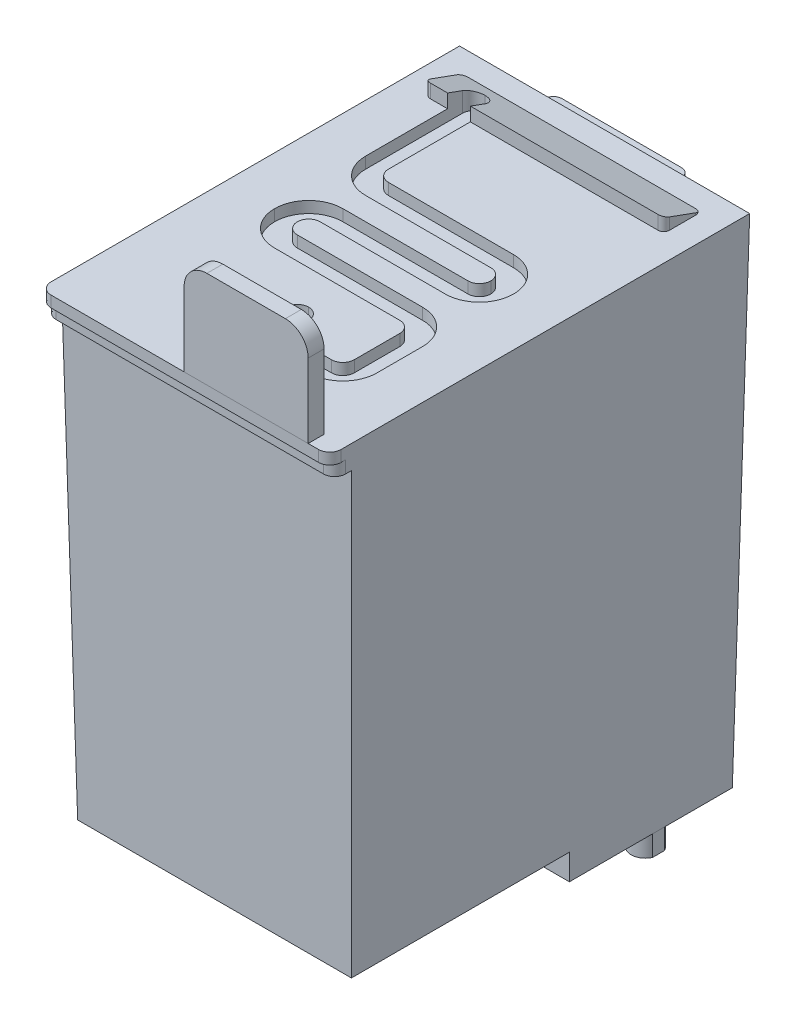
SolidWorks part; units mm, degrees
ref_plane "Front Plane" through (0, 0, 0) normal (0, 0, 1) x (1, 0, 0)
ref_plane "Top Plane" through (0, 0, 0) normal (0, 1, 0) x (1, 0, 0)
ref_plane "Right Plane" through (0, 0, 0) normal (1, 0, 0) x (0, 0, -1)
sketch "Sketch1" plane through (0, 0, 0) normal (0, 1, 0) x (1, 0, 0)
  line L0 (-12.75, 17.5) -> (12.75, -17.5) construction
  line L1 (-12.75, 17.5) -> (12.75, 17.5)
  line L2 (-12.75, 17.5) -> (-12.75, -17.5)
  line L3 (-12.75, -17.5) -> (12.75, -17.5)
  line L4 (12.75, 17.5) -> (12.75, -17.5)
  dimension "D1" = 25.5
  dimension "D2" = 35
extrude "Boss-Extrude1" add sketch "Sketch1" against normal blind 41.4 draft 1
sketch "Sketch2" plane through (0, -41.4, 0) normal (0, -1, 0) x (1, 0, 0)
  line L0 (-12.0274, -16.7774) -> (-12.0274, 16.7774) construction
  line L1 (12.0274, -16.7774) -> (-12.0274, -16.7774)
  line L2 (12.0274, -16.7774) -> (12.0274, -2.3774)
  line L3 (12.0274, -2.3774) -> (-12.0274, -2.3774)
  line L4 (-12.0274, -16.7774) -> (-12.0274, -2.3774)
  dimension "D1" = 14.4
extrude "Boss-Extrude2" add sketch "Sketch2" along normal blind 1.9 draft 1
sketch "Sketch3" plane through (0, -43.3, 0) normal (0, -1, 0) x (1, 0, 0)
  line L0 (-11.9942, -16.7442) -> (11.9942, -16.7442) construction
  line L1 (-5.2, -16.7442) -> (5.2, -16.7442)
  line L2 (-5.2, -16.7442) -> (-5.2, 16.7774)
  line L3 (-5.2, 16.7774) -> (5.2, 16.7774)
  line L4 (5.2, -16.7442) -> (5.2, 16.7774)
  line L5 (-12.0274, 16.7774) -> (12.0274, 16.7774) construction
  line L6 (0, 0) -> (0, 16.7774) construction
  dimension "D1" = 10.4
extrude "Boss-Extrude3" add sketch "Sketch3" along normal blind 1 and the other way up to next
sketch "Sketch4" plane through (5.2, 0, 0) normal (1, 0, 0) x (0, 0, -1)
  line L0 (16.7442, -43.3) -> (16.7267, -44.3)
  line L1 (16.7442, -44.3) -> (-16.7774, -44.3) construction
  line L2 (16.7267, -44.3) -> (16.7442, -44.3)
  line L3 (16.7442, -44.3) -> (16.7442, -43.3)
  line L4 (16.7442, -43.3) -> (17.5, 0) construction
extrude "Cut-Extrude1" cut sketch "Sketch4" against normal through all
sketch "Sketch5" plane through (0, -44.3, 0) normal (0, -1, 0) x (1, 0, 0)
  line L0 (5.2, -16.7267) -> (5.2, 16.7774) construction
  line L1 (-5.2, 16.7774) -> (5.2, 16.7774)
  line L2 (-5.2, 16.7774) -> (-5.2, -1.2267)
  line L3 (-5.2, -1.2267) -> (5.2, -1.2267)
  line L4 (5.2, 16.7774) -> (5.2, -1.2267)
  line L5 (-5.2, -16.7267) -> (5.2, -16.7267) construction
  dimension "D1" = 15.5
extrude "Boss-Extrude4" add sketch "Sketch5" along normal blind 0.4
sketch "Sketch6" plane through (5.2, 0, 0) normal (1, 0, 0) x (0, 0, -1)
  line L0 (-16.7774, -41.4) -> (-11.0616, -44.7)
  line L1 (1.2267, -44.7) -> (-16.7774, -44.7) construction
  line L2 (-11.0616, -44.7) -> (-16.7774, -44.7)
  line L3 (-16.7774, -44.7) -> (-16.7774, -41.4)
  dimension "D1" = 30
extrude "Cut-Extrude2" cut sketch "Sketch6" against normal through all
sketch "Sketch7" plane through (0, -44.7, 0) normal (0, -1, 0) x (1, 0, 0)
  line L0 (5.2, 16.7774) -> (-5.2, 16.7774) construction
  line L1 (-3.5, 16.7774) -> (3.5, 16.7774)
  line L2 (-3.5, 16.7774) -> (-3.5, 12.2774)
  line L3 (-3.5, 12.2774) -> (3.5, 12.2774)
  line L4 (3.5, 16.7774) -> (3.5, 12.2774)
  line L5 (0, 12.2774) -> (0, 11.0616) construction
  line L6 (-5.2, 11.0616) -> (5.2, 11.0616) construction
  dimension "D1" = 4.5
  dimension "D2" = 7
extrude "Cut-Extrude3" cut sketch "Sketch7" against normal up to surface (3.3 mm away) up to face at (-7.7603, -41.4, 4.8057)
sketch "Sketch8" plane through (0, -44.7, 0) normal (0, -1, 0) x (1, 0, 0)
  line L0 (0, 0) -> (0, -14.7267) construction
  line L1 (-4.2, 10.2774) -> (4.2, 10.2774)
  line L2 (-4.2, 10.2774) -> (-4.2, -14.7267)
  line L3 (-4.2, -14.7267) -> (4.2, -14.7267)
  line L4 (4.2, 10.2774) -> (4.2, -14.7267)
  line L5 (-5.2, -16.7267) -> (5.2, -16.7267) construction
  line L6 (-3.5, 12.2774) -> (3.5, 12.2774) construction
  dimension "D1" = 8.4
  dimension "D2" = 2
  dimension "D3" = 2
extrude "Cut-Extrude4" cut sketch "Sketch8" against normal blind 1.3
sketch "Sketch9" plane through (0, -43.3, 0) normal (0, -1, 0) x (1, 0, 0)
  line L0 (-11.9942, -16.7442) -> (-5.2, -16.7442) construction
  line L1 (-11.9942, -2.4105) -> (-9.6942, -2.4105)
  line L2 (-11.9942, -2.4105) -> (-11.9942, -16.7442)
  line L3 (-11.9942, -16.7442) -> (-9.6942, -16.7442)
  line L4 (-9.6942, -2.4105) -> (-9.6942, -16.7442)
  line L5 (5.2, -16.7442) -> (11.9942, -16.7442) construction
  line L6 (11.9942, -2.4105) -> (9.6942, -2.4105)
  line L7 (11.9942, -2.4105) -> (11.9942, -16.7442)
  line L8 (11.9942, -16.7442) -> (9.6942, -16.7442)
  line L9 (9.6942, -2.4105) -> (9.6942, -16.7442)
  dimension "D1" = 2.3
extrude "Boss-Extrude5" add sketch "Sketch9" along normal blind 0.4 draft 1
sketch "Sketch10" plane through (0, -43.7, 0) normal (0, -1, 0) x (1, 0, 0)
  line L0 (11.9872, -9.7183) -> (11.9872, -10.7561)
  line L1 (11.9872, -16.7372) -> (11.9872, -2.4175) construction
  line L2 (10.85, -10.2372) -> (-10.85, -10.2372) construction
  line L3 (0, -10.2372) -> (0, 0) construction
  line L4 (-11.9872, -16.7372) -> (-9.7012, -16.7372) construction
  circle A0 centre (-10.85, -10.2372) radius 1.25
  arc A1 (11.9872, -9.7183) -> (11.9872, -10.7561) centre (10.85, -10.2372) ccw
  dimension "D1" = 2.5
  dimension "D2" = 21.7
  dimension "D3" = 6.5
extrude "Boss-Extrude6" add sketch "Sketch10" along normal blind 1.8 and the other way up to next (43.7 mm away)
sketch "Sketch11" plane through (0, 0, 0) normal (0, 0, 1) x (1, 0, 0)
  line L0 (0, -1) -> (0, 0) construction
  line L1 (6, -1) -> (-6, -1)
  line L2 (6, -1) -> (6, -2.1)
  line L3 (6, -2.1) -> (-6, -2.1)
  line L4 (-6, -1) -> (-6, -2.1)
  line L5 (12.75, 0) -> (-12.75, 0) construction
  dimension "D1" = 12
  dimension "D2" = 1.1
  dimension "D3" = 1
extrude "Boss-Extrude7" add sketch "Sketch11" against normal blind 19
fillet "Fillet1" radius 0.75 2 edges at (-6, -1.55, -19) (6, -1.55, -19)
sketch "Sketch12" plane through (0, 0, 0) normal (0, 1, 0) x (1, 0, 0)
  line L0 (0, 12.2) -> (0, 0) construction
  line L1 (-10, 15.5) -> (10, 15.5)
  line L2 (-10.5, 15) -> (-10.5, 12.7)
  line L3 (-10, 12.2) -> (10, 12.2)
  line L4 (10.5, 15) -> (10.5, 12.7)
  line L5 (12.75, 17.5) -> (-12.75, 17.5) construction
  arc A0 (10, 15.5) -> (10.5, 15) centre (10, 15) cw
  arc A1 (-10.5, 12.7) -> (-10, 12.2) centre (-10, 12.7) ccw
  arc A2 (10, 12.2) -> (10.5, 12.7) centre (10, 12.7) ccw
  arc A3 (-10, 15.5) -> (-10.5, 15) centre (-10, 15) ccw
  dimension "D1" = 0.5
  dimension "D2" = 3.3
  dimension "D3" = 21
  dimension "D4" = 2
extrude "Boss-Extrude8" add sketch "Sketch12" along normal blind 1.5
chamfer "Chamfer1" distance 1.5 angle 70 1 edges at (0, 1.5, -15.5) tangent propagation no first distance on face at (0, 0.75, -15.5)
sketch "Sketch13" plane through (0, 0, 0) normal (0, 1, 0) x (1, 0, 0)
  line L0 (-12.75, 17.5) -> (-12.75, -17.5) construction
  line L1 (-12.75, 0) -> (12.75, 0)
  line L2 (-12.75, 0) -> (-12.75, -18.4)
  line L3 (-11.75, -19.4) -> (11.75, -19.4)
  line L4 (12.75, 0) -> (12.75, -18.4)
  line L5 (12.75, -17.5) -> (12.75, 17.5) construction
  line L6 (-12.75, -17.5) -> (12.75, -17.5) construction
  arc A0 (-12.75, -18.4) -> (-11.75, -19.4) centre (-11.75, -18.4) ccw
  arc A1 (11.75, -19.4) -> (12.75, -18.4) centre (11.75, -18.4) ccw
  dimension "D1" = 1
  dimension "D2" = 1.9
extrude "Boss-Extrude9" add sketch "Sketch13" against normal blind 1 draft 1
sketch "Sketch14" plane through (0, 0, 0) normal (0, 1, 0) x (1, 0, 0)
  line L0 (-12.75, 17.5) -> (-12.75, -18.4) construction
  line L1 (-12.75, -0.45) -> (12.75, -0.45)
  line L2 (-12.75, -0.45) -> (-12.75, -17.9825)
  line L3 (-11.75, -18.9825) -> (11.75, -18.9825)
  line L4 (12.75, -0.45) -> (12.75, -17.9825)
  line L5 (12.75, -18.4) -> (12.75, 17.5) construction
  line L6 (12.7325, -17.4825) -> (-12.7325, -17.4825) construction
  arc A0 (-12.75, -17.9825) -> (-11.75, -18.9825) centre (-11.75, -17.9825) ccw
  arc A1 (11.75, -18.9825) -> (12.75, -17.9825) centre (11.75, -17.9825) ccw
  point P12 (12.75, -18.9825)
  dimension "D1" = 1
  dimension "D2" = 1.5
extrude "Boss-Extrude10" add sketch "Sketch14" against normal blind 2.1 draft 1
sketch "Sketch15" plane through (0, 0, 0) normal (0, 1, 0) x (1, 0, 0)
  line L0 (-11.75, -19.4) -> (11.75, -19.4) construction
  line L1 (10.85, -19.4) -> (-0.05, -19.4)
  line L2 (10.85, -19.4) -> (10.85, -18)
  line L3 (10.85, -18) -> (-0.05, -18)
  line L4 (-0.05, -19.4) -> (-0.05, -18)
  line L6 (-12.75, 17.5) -> (-12.75, -18.4) construction
  dimension "D1" = 10.9
  dimension "D2" = 23.6
  dimension "D3" = 1.4
extrude "Boss-Extrude11" add sketch "Sketch15" along normal blind 8.5
fillet "Fillet2" radius 2 2 edges at (10.85, 8.5, 18.7) (-0.05, 8.5, 18.7)
sketch "Sketch16" plane through (0, 0, 0) normal (0, 1, 0) x (1, 0, 0)
  line L0 (-8.5, 14.5) -> (-8.5, 2)
  line L1 (-8.5, 2) -> (6.5, 2)
  line L2 (6.5, 2) -> (6.5, 0)
  line L3 (6.5, 0) -> (-8.5, 0)
  line L4 (-8.5, 0) -> (-8.5, -6)
  line L5 (-8.5, -6) -> (6.5, -6)
  line L6 (6.5, -6) -> (6.5, -12)
  line L7 (6.5, -12) -> (1.5, -12)
  line L8 (1.5, -12) -> (1.5, -9)
  line L9 (1.5, -9) -> (-0.5, -9)
  line L10 (-0.5, -9) -> (-0.5, -14)
  line L11 (-0.5, -14) -> (8.5, -14)
  line L12 (8.5, -14) -> (8.5, -4)
  line L13 (8.5, -4) -> (-6.5, -4)
  line L14 (-6.5, -4) -> (-6.5, -2)
  line L15 (-6.5, -2) -> (8.5, -2)
  line L16 (8.5, -2) -> (8.5, 4)
  line L17 (8.5, 4) -> (-6.5, 4)
  line L18 (-6.5, 4) -> (-6.5, 14.5)
  line L19 (-6.5, 14.5) -> (-8.5, 14.5)
  line L20 (-6.5, 4) -> (-6.5, 2) construction
  line L21 (6.5, 2) -> (8.5, 2) construction
  line L22 (6.5, 0) -> (6.5, -2) construction
  line L23 (-6.5, -2) -> (-8.5, -2) construction
  line L24 (6.5, -6) -> (6.5, -4) construction
  line L25 (6.5, -12) -> (8.5, -12) construction
  line L26 (1.5, -12) -> (1.5, -14) construction
  line L27 (10, 15.5) -> (-10, 15.5) construction
  line L28 (-10.5, 15) -> (-10.5, 12.7) construction
  line L29 (1, -2) -> (-1, 0) construction
  line L30 (0, -1) -> (0, 0) construction
  dimension "D1" = 2
  dimension "D2" = 1
  dimension "D3" = 2
  dimension "D4" = 2
  dimension "D5" = 2
  dimension "D6" = 5
  dimension "D7" = 3
  dimension "D8" = 10.5
  dimension "D9" = 3
extrude "Cut-Extrude5" cut sketch "Sketch16" against normal blind 1 and the other way through all
fillet "Fillet3" radius 1 12 edges at (-0.5, -0.5, 9) (1.5, -0.5, 9) (1.5, -0.5, 12) (6.5, -0.5, 12) (6.5, -0.5, 6) (-6.5, -0.5, 2) (-6.5, -0.5, 4) (6.5, -0.5, 0) (6.5, -0.5, -2) (-6.5, -0.5, -4) (-8.5, -0.318, -14.5) (-6.5, -0.318, -14.5)
fillet "Fillet4" radius 3 8 edges at (-8.5, -0.5, -2) (8.5, -0.5, 14) (-0.5, -0.5, 14) (8.5, -0.5, 4) (8.5, -0.5, -4) (8.5, -0.5, 2) (-8.5, -0.5, 6) (-8.5, -0.5, 0)
sketch "Sketch17" plane through (0, -43.4, 0) normal (0, -1, 0) x (1, 0, 0)
  line L1 (-3.25, 10.0774) -> (3.25, 10.0774)
  line L2 (-3.25, 10.0774) -> (-3.25, -14.5267)
  line L3 (-3.25, -14.5267) -> (3.25, -14.5267)
  line L4 (3.25, 10.0774) -> (3.25, -14.5267)
  line L5 (0, -14.5267) -> (0, -14.7267) construction
  line L6 (-4.2, -14.7267) -> (4.2, -14.7267) construction
  line L7 (0, 10.0774) -> (0, 10.2774) construction
  line L8 (4.2, 10.2774) -> (-4.2, 10.2774) construction
  dimension "D1" = 0.2
  dimension "D2" = 6.5
extrude "Boss-Extrude12" add sketch "Sketch17" along normal blind 1
sketch "Sketch18" plane through (0, -44.4, 0) normal (0, -1, 0) x (1, 0, 0)
  line L0 (3.25, 10.0774) -> (-3.25, 10.0774) construction
  line L1 (-1.35, 9.8774) -> (3.05, 9.8774)
  line L2 (-1.35, 9.8774) -> (-1.35, 2.3774)
  line L3 (-1.35, 2.3774) -> (3.05, 2.3774)
  line L4 (3.05, 9.8774) -> (3.05, 2.3774)
  line L5 (3.25, -14.5267) -> (3.25, 10.0774) construction
  dimension "D1" = 4.4
  dimension "D2" = 7.5
  dimension "D3" = 0.2
  dimension "D4" = 0.2
extrude "Boss-Extrude13" add sketch "Sketch18" along normal blind 0.1
sketch "Sketch19" plane through (0, -44.4, 0) normal (0, -1, 0) x (1, 0, 0)
  line L0 (-2.15, -13.9017) -> (1.8, -13.9017) construction
  line L1 (-3.15, -13.4767) -> (-2.15, -13.4767)
  line L2 (-3.15, -13.4767) -> (-3.15, -14.3267)
  line L3 (-3.15, -14.3267) -> (-2.15, -14.3267)
  line L4 (-2.15, -13.4767) -> (-2.15, -14.3267)
  line L5 (1.8, -13.4767) -> (2.8, -13.4767)
  line L6 (1.8, -13.4767) -> (1.8, -14.3267)
  line L7 (1.8, -14.3267) -> (2.8, -14.3267)
  line L8 (2.8, -13.4767) -> (2.8, -14.3267)
  line L9 (-3.25, 10.0774) -> (-3.25, -14.5267) construction
  line L10 (3.25, -14.5267) -> (3.25, 10.0774) construction
  line L11 (-3.25, -14.5267) -> (3.25, -14.5267) construction
  line L12 (-3.15, -12.0851) -> (-2.15, -12.0851)
  line L13 (-3.15, -12.0851) -> (-3.15, -12.9351)
  line L14 (-3.15, -12.9351) -> (-2.15, -12.9351)
  line L15 (-2.15, -12.0851) -> (-2.15, -12.9351)
  line L16 (-3.15, -10.6934) -> (-2.15, -10.6934)
  line L17 (-3.15, -10.6934) -> (-3.15, -11.5434)
  line L18 (-3.15, -11.5434) -> (-2.15, -11.5434)
  line L19 (-2.15, -10.6934) -> (-2.15, -11.5434)
  line L20 (-3.15, -9.3017) -> (-2.15, -9.3017)
  line L21 (-3.15, -9.3017) -> (-3.15, -10.1517)
  line L22 (-3.15, -10.1517) -> (-2.15, -10.1517)
  line L23 (-2.15, -9.3017) -> (-2.15, -10.1517)
  line L24 (-3.15, -7.9101) -> (-2.15, -7.9101)
  line L25 (-3.15, -7.9101) -> (-3.15, -8.7601)
  line L26 (-3.15, -8.7601) -> (-2.15, -8.7601)
  line L27 (-2.15, -7.9101) -> (-2.15, -8.7601)
  line L28 (-3.15, -6.5184) -> (-2.15, -6.5184)
  line L29 (-3.15, -6.5184) -> (-3.15, -7.3684)
  line L30 (-3.15, -7.3684) -> (-2.15, -7.3684)
  line L31 (-2.15, -6.5184) -> (-2.15, -7.3684)
  line L32 (-3.15, -5.1267) -> (-2.15, -5.1267)
  line L33 (-3.15, -5.1267) -> (-3.15, -5.9767)
  line L34 (-3.15, -5.9767) -> (-2.15, -5.9767)
  line L35 (-2.15, -5.1267) -> (-2.15, -5.9767)
  line L36 (1.8, -12.0851) -> (2.8, -12.0851)
  line L37 (1.8, -12.0851) -> (1.8, -12.9351)
  line L38 (1.8, -12.9351) -> (2.8, -12.9351)
  line L39 (2.8, -12.0851) -> (2.8, -12.9351)
  line L40 (1.8, -10.6934) -> (2.8, -10.6934)
  line L41 (1.8, -10.6934) -> (1.8, -11.5434)
  line L42 (1.8, -11.5434) -> (2.8, -11.5434)
  line L43 (2.8, -10.6934) -> (2.8, -11.5434)
  line L44 (1.8, -9.3017) -> (2.8, -9.3017)
  line L45 (1.8, -9.3017) -> (1.8, -10.1517)
  line L46 (1.8, -10.1517) -> (2.8, -10.1517)
  line L47 (2.8, -9.3017) -> (2.8, -10.1517)
  line L48 (1.8, -7.9101) -> (2.8, -7.9101)
  line L49 (1.8, -7.9101) -> (1.8, -8.7601)
  line L50 (1.8, -8.7601) -> (2.8, -8.7601)
  line L51 (2.8, -7.9101) -> (2.8, -8.7601)
  line L52 (1.8, -6.5184) -> (2.8, -6.5184) construction
  line L53 (1.8, -6.5184) -> (1.8, -7.3684)
  line L54 (1.8, -7.3684) -> (2.8, -7.3684)
  line L55 (2.8, -6.5184) -> (2.8, -7.3684)
  line L56 (1.8, -5.1267) -> (2.8, -5.1267)
  line L57 (1.8, -5.1267) -> (1.8, -5.9767)
  line L58 (1.8, -5.9767) -> (2.8, -5.9767) construction
  line L59 (2.8, -5.1267) -> (2.8, -5.9767)
  line L60 (1.8, -5.9767) -> (1.8, -6.5184)
  line L61 (2.8, -6.5184) -> (2.8, -5.9767)
  dimension "D1" = 0.85
  dimension "D2" = 1
  dimension "D3" = 0.1
  dimension "D4" = 0.45
  dimension "D5" = 0.2
  dimension "D7" = 9.2
  dimension "D6" = 7
  dimension "D8" = 7
extrude "Boss-Extrude14" add sketch "Sketch19" along normal blind 0.1
